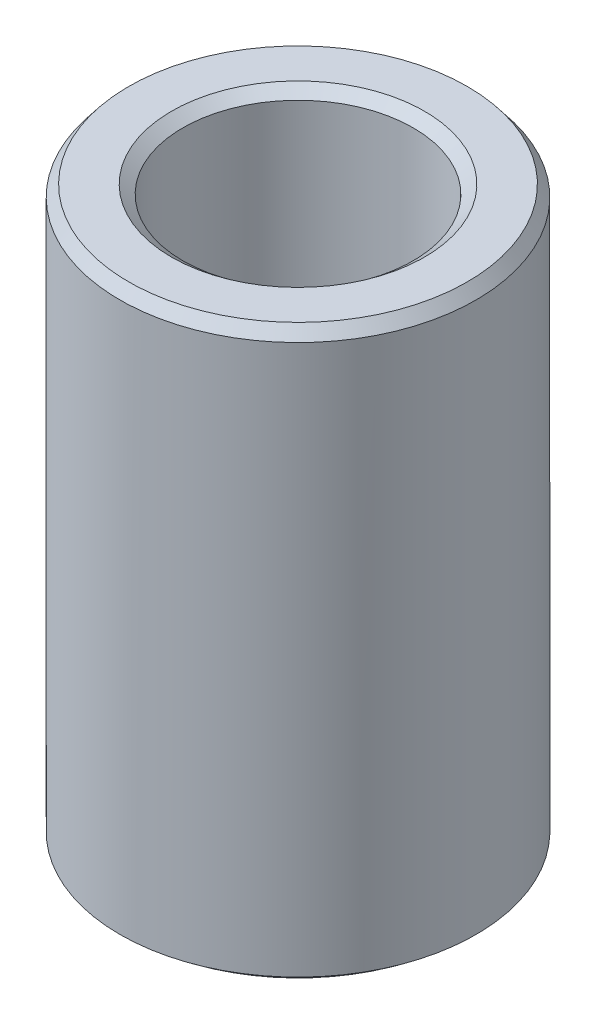
SolidWorks part; units mm, degrees
ref_plane "Front Plane" through (0, 0, 0) normal (0, 0, 1) x (1, 0, 0)
ref_plane "Top Plane" through (0, 0, 0) normal (0, 1, 0) x (1, 0, 0)
ref_plane "Right Plane" through (0, 0, 0) normal (1, 0, 0) x (0, 0, -1)
sketch "Sketch1" plane through (0, 0, 0) normal (0, 1, 0) x (1, 0, 0)
  circle A0 centre (0, 0) radius 40
  dimension "SLEEVE_OD" = 80
extrude "Boss-Extrude1" add sketch "Sketch1" along normal blind 127.9482
sketch "Sketch2" plane through (0, 0, 0) normal (0, 1, 0) x (1, 0, 0)
  circle A0 centre (0, 0) radius 25.8753
  dimension "BORE_D" = 51.7506
extrude "Cut-Extrude1" cut sketch "Sketch2" along normal through all
chamfer "Chamfer1" distance 2.5346 angle 37.813 4 edges at (0, 127.9482, 25.8753) (0, 0, 25.8753) (0, 0, 40) (0, 127.9482, 40) first distance on face at (0, 127.9482, 25.8753) first distance on face at (0, 0, 25.8753) first distance on face at (0, 127.9482, 40)
